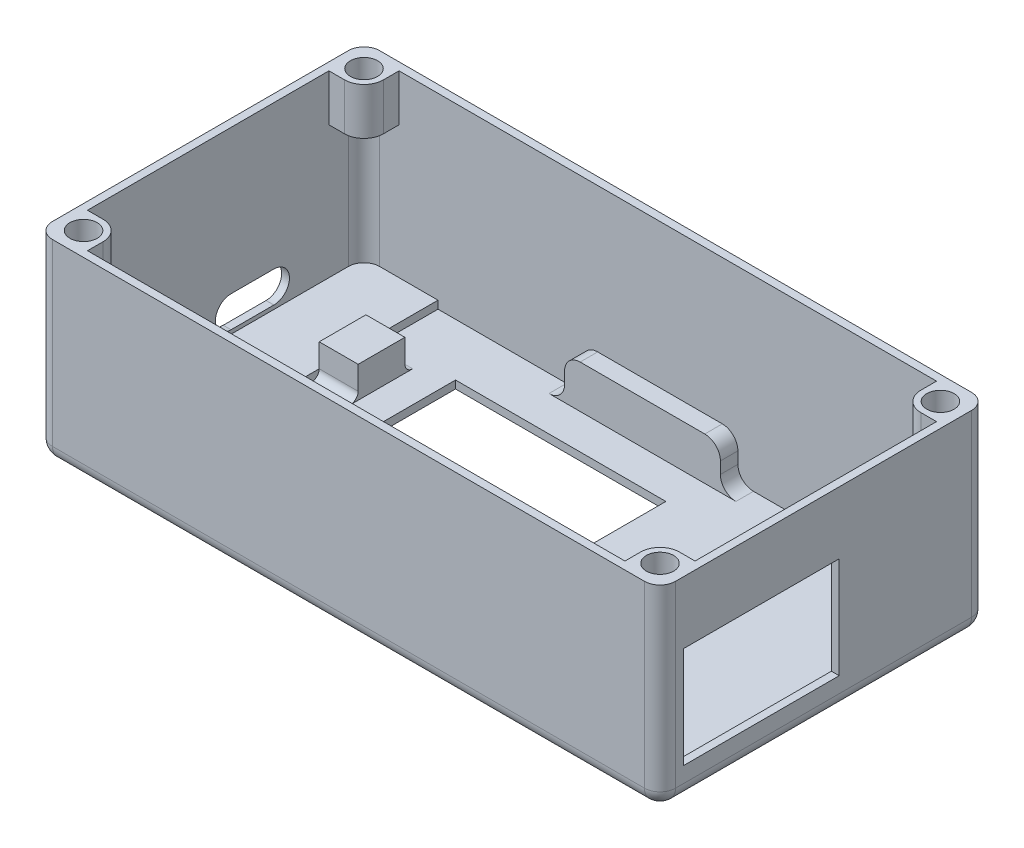
SolidWorks part; units mm, degrees
ref_plane "Front Plane" through (0, 0, 0) normal (0, 0, 1) x (1, 0, 0)
ref_plane "Top Plane" through (0, 0, 0) normal (0, 1, 0) x (1, 0, 0)
ref_plane "Right Plane" through (0, 0, 0) normal (1, 0, 0) x (0, 0, -1)
sketch "Sketch1" plane through (0, 0, 0) normal (0, 1, 0) x (1, 0, 0)
  line L1 (-40, -21) -> (40, -21)
  line L2 (-40, -21) -> (-40, 21)
  line L3 (-40, 21) -> (40, 21)
  line L4 (40, -21) -> (40, 21)
  line L5 (-40, -21) -> (40, 21) construction
  line L6 (-40, 21) -> (40, -21) construction
  point P0 (0, 0)
  dimension "D1" = 80
  dimension "D2" = 42
extrude "Boss-Extrude1" add sketch "Sketch1" along normal blind 25
sketch "Sketch6" plane through (0, 25, 0) normal (0, 1, 0) x (1, 0, 0)
  line L0 (40, -21) -> (40, 21) construction
  line L1 (-39, 20) -> (39, 20)
  line L2 (-39, 20) -> (-39, -20)
  line L3 (-39, -20) -> (39, -20)
  line L4 (39, 20) -> (39, -20)
  line L5 (-39, 20) -> (39, -20) construction
  line L6 (-39, -20) -> (39, 20) construction
  line L7 (-40, -21) -> (40, -21) construction
  point P0 (0, 0)
  dimension "D1" = 1
  dimension "D2" = 1
extrude "Cut-Extrude6" cut sketch "Sketch6" against normal offset from surface (24 mm away) 1 up to face at (0, 0, 0)
sketch "Sketch7" plane through (0, 1, 0) normal (0, 1, 0) x (1, 0, 0)
  line L0 (-40, 21) -> (-40, -21) construction
  line L1 (-24.5, 17.75) -> (9, 17.75)
  line L2 (-24.5, 17.75) -> (-24.5, -2.25)
  line L3 (-24.5, -2.25) -> (9, -2.25)
  line L4 (9, 17.75) -> (9, -2.25)
  line L5 (-24.5, 17.75) -> (9, -2.25) construction
  line L6 (-24.5, -2.25) -> (9, 17.75) construction
  line L8 (39, 20) -> (-39, 20) construction
  point P0 (-7.75, 7.75)
  dimension "D1" = 20
  dimension "D2" = 33.5
  dimension "D3" = 15.5
  dimension "D4" = 2.25
extrude "Cut-Extrude7" cut sketch "Sketch7" against normal up to next
sketch "Sketch8" plane through (0, 1, 0) normal (0, 1, 0) x (1, 0, 0)
  line L0 (-24.5, 17.75) -> (-24.5, -2.25) construction
  line L1 (-29.5, 10.75) -> (-24.5, 10.75)
  line L2 (-29.5, 10.75) -> (-29.5, 4.75)
  line L3 (-29.5, 4.75) -> (-24.5, 4.75)
  line L4 (-24.5, 10.75) -> (-24.5, 4.75)
  line L5 (-29.5, 10.75) -> (-24.5, 4.75) construction
  line L6 (-29.5, 4.75) -> (-24.5, 10.75) construction
  point P0 (-27, 7.75)
  point P5 (-29.2666, 5.2771)
  point P6 (0, 0)
  point P9 (-24.5, 7.75)
  dimension "D1" = 6
  dimension "D2" = 5
extrude "Boss-Extrude2" add sketch "Sketch8" along normal blind 4
sketch "Sketch9" plane through (0, 1, 0) normal (0, 1, 0) x (1, 0, 0)
  line L1 (-39, 20) -> (-29.5, 20)
  line L2 (-39, 20) -> (-39, -5.25)
  line L3 (-39, -5.25) -> (-29.5, -5.25)
  line L4 (-29.5, 20) -> (-29.5, -5.25)
  line L5 (-29.5, 10.75) -> (-29.5, 4.75) construction
  line L6 (-24.5, -2.25) -> (9, -2.25) construction
  point P5 (-30.5, -9.7447)
  dimension "D1" = 3
extrude "Boss-Extrude3" add sketch "Sketch9" along normal blind 1
fillet "Fillet1" radius 1 2 edges at (-27, 1, -10.75) (-27, 1, -4.75)
fillet "Fillet3" radius 2 8 edges at (-39, 13, 20) (39, 13, 20) (39, 13, -20) (-39, 13.5, -20) (40, 12.5, -21) (-40, 12.5, -21) (-40, 12.5, 21) (40, 12.5, 21)
sketch "Sketch16" plane through (0, 1, 0) normal (0, 1, 0) x (1, 0, 0)
  line L0 (39, -18) -> (39, 18) construction
  line L1 (24, -2.25) -> (37, -2.25)
  line L2 (24, -2.25) -> (24, 17.75)
  line L3 (24, 17.75) -> (37, 17.75)
  line L4 (37, -2.25) -> (37, 17.75)
  line L5 (24, -2.25) -> (37, 17.75) construction
  line L6 (24, 17.75) -> (37, -2.25) construction
  line L9 (9, 17.75) -> (-24.5, 17.75) construction
  point P0 (30.5, 7.75)
  point P5 (0, 0)
  point P6 (24.5342, -5.7241)
  dimension "D1" = 13
  dimension "D2" = 20
  dimension "D3" = 2
extrude "Cut-Extrude11" [suppressed] cut sketch "Sketch16" against normal up to next
sketch "Sketch12" plane through (-39, 0, 0) normal (1, 0, 0) x (0, 0, -1)
  line L0 (5.6788, 1) -> (5.6788, 4.5) construction
  line L4 (-5.25, 1) -> (-18, 1) construction
  line L5 (2.9288, 4.5) -> (8.4288, 4.5) construction
  line L6 (2.9288, 6.5) -> (8.4288, 6.5)
  line L7 (2.9288, 2.5) -> (8.4288, 2.5)
  arc A0 (2.9288, 6.5) -> (2.9288, 2.5) centre (2.9288, 4.5) ccw
  arc A1 (8.4288, 2.5) -> (8.4288, 6.5) centre (8.4288, 4.5) ccw
  point P4 (5.6788, 4.5)
  point P11 (0.9288, 4.5)
  point P12 (10.4288, 4.5)
  dimension "D1" = 3.5
  dimension "D2" = 4
  dimension "D3" = 9.5
extrude "Cut-Extrude8" cut sketch "Sketch12" against normal up to next
sketch "Sketch18" plane through (0, 1, 0) normal (0, 1, 0) x (1, 0, 0)
  line L0 (37, 20) -> (-29.5, 20) construction
  line L1 (9, 17.75) -> (-11, 17.75)
  line L2 (9, 17.75) -> (9, 20)
  line L3 (9, 20) -> (-11, 20)
  line L4 (-11, 17.75) -> (-11, 20)
  line L5 (-39, -5.25) -> (-29.5, -5.25) construction
  line L6 (9, -2.25) -> (-11, -2.25)
  line L7 (9, -2.25) -> (9, -5.25)
  line L8 (9, -5.25) -> (-11, -5.25)
  line L9 (-11, -2.25) -> (-11, -5.25)
  point P14 (0, 0)
  dimension "D1" = 20
extrude "Boss-Extrude5" add sketch "Sketch18" along normal up to surface (5.5 mm away) up to face at (-39.5, 6.5, -5.6788)
fillet "Fillet5" radius 2 8 edges at (-11, 1, 3.75) (9, 1, 3.75) (9, 6.5, 3.75) (-11, 6.5, 3.75) (9, 6.5, -18.875) (-11, 6.5, -18.875) (-11, 1, -18.875) (9, 1, -18.875)
sketch "Sketch19" plane through (-40, 0, 0) normal (-1, 0, 0) x (0, 0, 1)
  line L0 (13, 0) -> (13, 7.5) construction
  line L1 (-19, 0) -> (19, 0) construction
  line L3 (19, 0) -> (19, 25) construction
  line L5 (10, 8.75) -> (10, 6.25)
  arc A0 (10, 6.25) -> (10, 8.75) centre (13, 7.5) ccw
  arc A1 (10, 8.75) -> (10, 6.25) centre (13, 7.5) ccw construction
  point P7 (13, 3.75)
  dimension "D3" = 6.5
  dimension "D1" = 6
  dimension "D2" = 7.5
  dimension "D4" = 3
extrude "Cut-Extrude12" cut sketch "Sketch19" against normal up to next
sketch "Sketch20" plane through (0, 25, 0) normal (0, 1, 0) x (1, 0, 0)
  line L0 (37, 20) -> (-37, 20) construction
  line L4 (-39, 18) -> (-39, -5.25) construction
  line L5 (-34.5, 20) -> (-37, 20)
  line L9 (-39, 18) -> (-39, 15.5)
  line L10 (-37, 15.5) -> (-39, 15.5)
  line L11 (-34.5, 18) -> (-34.5, 20)
  arc A3 (-37, 20) -> (-39, 18) centre (-37, 18) ccw construction
  arc A7 (-37, 20) -> (-39, 18) centre (-37, 18) ccw
  arc A8 (-37, 15.5) -> (-34.5, 18) centre (-37, 18) ccw
  dimension "D1" = 5
extrude "Boss-Extrude6" add sketch "Sketch20" against normal blind 6
sketch "Sketch22" plane through (0, 25, 0) normal (0, 1, 0) x (1, 0, 0)
  line L4 (40, -19) -> (40, 19)
  line L5 (38, 21) -> (-38, 21)
  line L6 (-40, 19) -> (-40, -19)
  line L7 (-38, -21) -> (38, -21)
  line L8 (40, -19) -> (40, 19)
  line L9 (38, 21) -> (-38, 21)
  line L10 (-40, 19) -> (-40, -19)
  line L11 (-38, -21) -> (38, -21)
  circle A0 centre (-37, 18) radius 1.75
  arc A4 (40, 19) -> (38, 21) centre (38, 19) ccw
  arc A5 (-38, 21) -> (-40, 19) centre (-38, 19) ccw
  arc A6 (-40, -19) -> (-38, -21) centre (-38, -19) ccw
  arc A7 (38, -21) -> (40, -19) centre (38, -19) ccw
  arc A8 (40, 19) -> (38, 21) centre (38, 19) ccw
  arc A9 (-38, 21) -> (-40, 19) centre (-38, 19) ccw
  arc A10 (-40, -19) -> (-38, -21) centre (-38, -19) ccw
  arc A11 (38, -21) -> (40, -19) centre (38, -19) ccw
  point P2 (-37, 18)
  dimension "D2" = 3.5
  dimension "D1" = 0
extrude "Cut-Extrude13" cut sketch "Sketch22" against normal up to next contours A0
mirror "Mirror1" about plane through (0, 0, 0) normal (0, 0, 1) of "Cut-Extrude13", "Boss-Extrude6"
mirror "Mirror3" about plane through (0, 0, 0) normal (1, 0, 0) of "Mirror1", "Cut-Extrude13", "Boss-Extrude6"
fillet "Fillet6" radius 2 8 edges at (-39.4142, 0, 20.4142) (-40, 0, 0) (-39.4142, 0, -20.4142) (0, 0, -21) (39.4142, 0, -20.4142) (40, 0, 0) (39.4142, 0, 20.4142) (0, 0, 21)
sketch "Sketch23" plane through (0, 0, 0) normal (0, -1, 0) x (1, 0, 0)
  line L0 (-20.5, 2.25) -> (-20.5, -13.25)
  line L1 (-24.5, 2.25) -> (9, 2.25) construction
  line L2 (-20.5, -13.25) -> (6.5, -13.25)
  line L3 (6.5, -13.25) -> (6.5, 2.25)
  line L4 (6.5, 2.25) -> (9, 2.25)
  line L5 (9, 2.25) -> (9, -17.75)
  line L6 (9, -17.75) -> (-24.5, -17.75)
  line L7 (-24.5, -17.75) -> (-24.5, 2.25)
  line L8 (-24.5, 2.25) -> (-20.5, 2.25)
  point P12 (-23.5854, 3.25)
  dimension "D1" = 4.5
  dimension "D2" = 4
  dimension "D3" = 2.5
extrude "Boss-Extrude7" add sketch "Sketch23" against normal up to surface (1 mm away) up to face at (-22.3333, 1, -16.5)
sketch "Sketch24" plane through (40, 0, 0) normal (1, 0, 0) x (0, 0, -1)
  line L0 (-19, 25) -> (-19, 2) construction
  line L1 (-18, 17) -> (2, 17)
  line L2 (-18, 17) -> (-18, 4)
  line L3 (-18, 4) -> (2, 4)
  line L4 (2, 17) -> (2, 4)
  line L5 (-18, 17) -> (2, 4) construction
  line L6 (-18, 4) -> (2, 17) construction
  line L7 (-19, 2) -> (19, 2) construction
  point P0 (-8, 10.5)
  dimension "D1" = 13
  dimension "D2" = 20
  dimension "D3" = 1
  dimension "D4" = 2
extrude "Cut-Extrude14" cut sketch "Sketch24" against normal up to next
